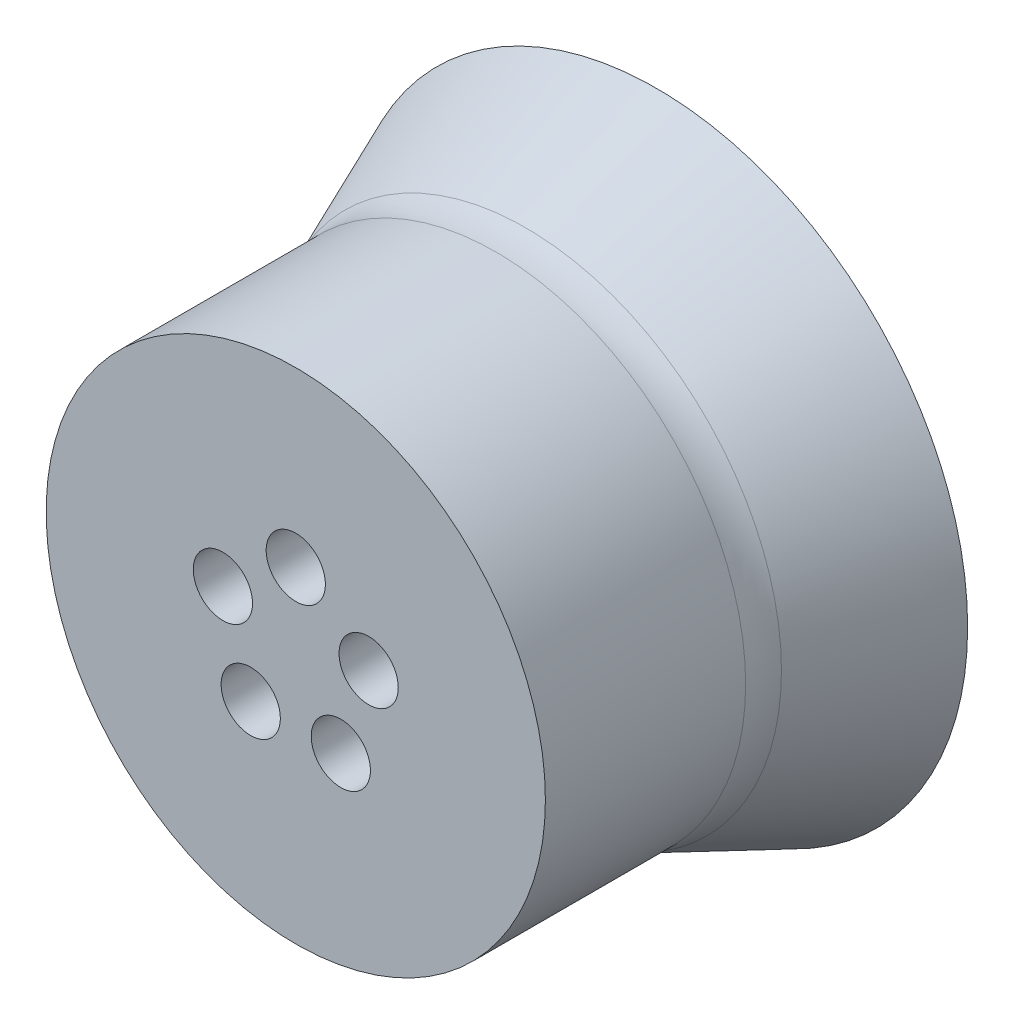
SolidWorks part; units mm, degrees
ref_plane "Front Plane" through (0, 0, 0) normal (0, 0, 1) x (1, 0, 0)
ref_plane "Top Plane" through (0, 0, 0) normal (0, 1, 0) x (1, 0, 0)
ref_plane "Right Plane" through (0, 0, 0) normal (1, 0, 0) x (0, 0, -1)
sketch "Sketch1" plane through (0, 0, 0) normal (0, 1, 0) x (1, 0, 0)
  line L1 (-23.1775, -34.925) -> (23.1775, -34.925) construction
  line L2 (34.925, -34.925) -> (34.925, 0)
  line L3 (34.925, 0) -> (37.465, 0)
  line L4 (37.465, 0) -> (46.6729, 16.7019)
  line L5 (46.6729, 16.7019) -> (38.371, -2.94)
  line L6 (37.465, -7.4107) -> (37.465, -37.465)
  line L7 (37.465, -37.465) -> (0, -37.465)
  line L8 (0, -37.465) -> (0, -34.925)
  line L9 (-23.1775, -34.925) -> (23.1775, -34.925) construction
  line L10 (20.0938, -31.8413) -> (-20.0938, -31.8413) construction
  line L11 (20.0938, -31.8413) -> (-20.0938, -31.8413) construction
  line L12 (-14.8504, -16.51) -> (14.8504, -16.51) construction
  line L13 (-17.9342, -19.5937) -> (17.9342, -19.5937) construction
  line L14 (-14.8504, -16.51) -> (14.8504, -16.51) construction
  line L15 (-17.9342, -19.5937) -> (17.9342, -19.5937) construction
  line L16 (23.1775, -34.925) -> (20.0938, -31.8413) construction
  line L17 (20.0938, -31.8413) -> (17.9342, -19.5937) construction
  line L18 (17.9342, -19.5937) -> (14.8504, -16.51) construction
  line L19 (14.8504, -16.51) -> (0, -16.51) construction
  line L20 (0, -16.51) -> (0, -34.925)
  line L21 (34.925, -34.925) -> (23.1775, -34.925)
  line L22 (22.8947, -34.925) -> (19.9077, -31.9381)
  line L23 (19.9077, -31.9381) -> (17.7482, -19.6906)
  line L24 (17.7482, -19.6906) -> (14.7676, -16.71)
  line L25 (14.7676, -16.71) -> (0, -16.71)
  line L26 (23.1775, -34.925) -> (22.8947, -34.925)
  line L27 (23.0361, -35.0664) -> (19.9077, -31.9381) construction
  arc A0 (38.371, -2.94) -> (37.465, -7.4107) centre (48.9484, -7.4107) ccw
  dimension "D1" = 2.54
  dimension "D3" = 11.4834
  dimension "D2" = 2.54
  dimension "D4" = 2.94
  dimension "D5" = 0.2
revolve "Revolve1" add sketch "Sketch1" angle 360 about L8 region at (16.725, 0, 25.2588)
sketch "Sketch3" plane through (0, 0, 37.465) normal (0, 0, 1) x (1, 0, 0)
  circle A0 centre (6.7595, -9.3037) radius 4.445
  circle A1 centre (10.9371, 3.5537) radius 1.8288
  circle A2 centre (10.9371, 3.5537) radius 1.8288
  circle A3 centre (0, 11.5) radius 1.8288
  circle A4 centre (0, 11.5) radius 1.8288
  circle A5 centre (-10.9371, 3.5537) radius 1.8288
  circle A6 centre (-10.9371, 3.5537) radius 1.8288
  circle A7 centre (-6.7595, -9.3037) radius 1.8288
  circle A8 centre (-6.7595, -9.3037) radius 1.8288
  circle A9 centre (6.7595, -9.3037) radius 1.8288
  circle A10 centre (6.7595, -9.3037) radius 1.8288
  circle A11 centre (-6.7595, -9.3037) radius 4.445
  circle A12 centre (-10.9371, 3.5537) radius 4.445
  circle A13 centre (0, 11.5) radius 4.445
  circle A14 centre (10.9371, 3.5537) radius 4.445
  dimension "D6" = 8.89
  dimension "D1" = 0
  dimension "D2" = 0
  dimension "D3" = 0
  dimension "D4" = 0
  dimension "D5" = 0
extrude "Cut-Extrude1" cut sketch "Sketch3" against normal through all contours A4 | A6 | A8 | A10 | A2
extrude "Cut-Extrude2" cut sketch "Sketch3<3>" against normal blind 12.7 contours A12 | A13 | A11 | A0 | A14
sketch "Sketch3<3>" plane through (0, 0, 37.465) normal (0, 0, 1) x (1, 0, 0) same geometry as "Sketch3"
fillet "Fillet1" radius 3.048 5 edges at (-2.3145, -9.3037, 24.765) (11.2045, -9.3037, 24.765) (15.3821, 3.5537, 24.765) (4.445, 11.5, 24.765) (-6.4921, 3.5537, 24.765)
